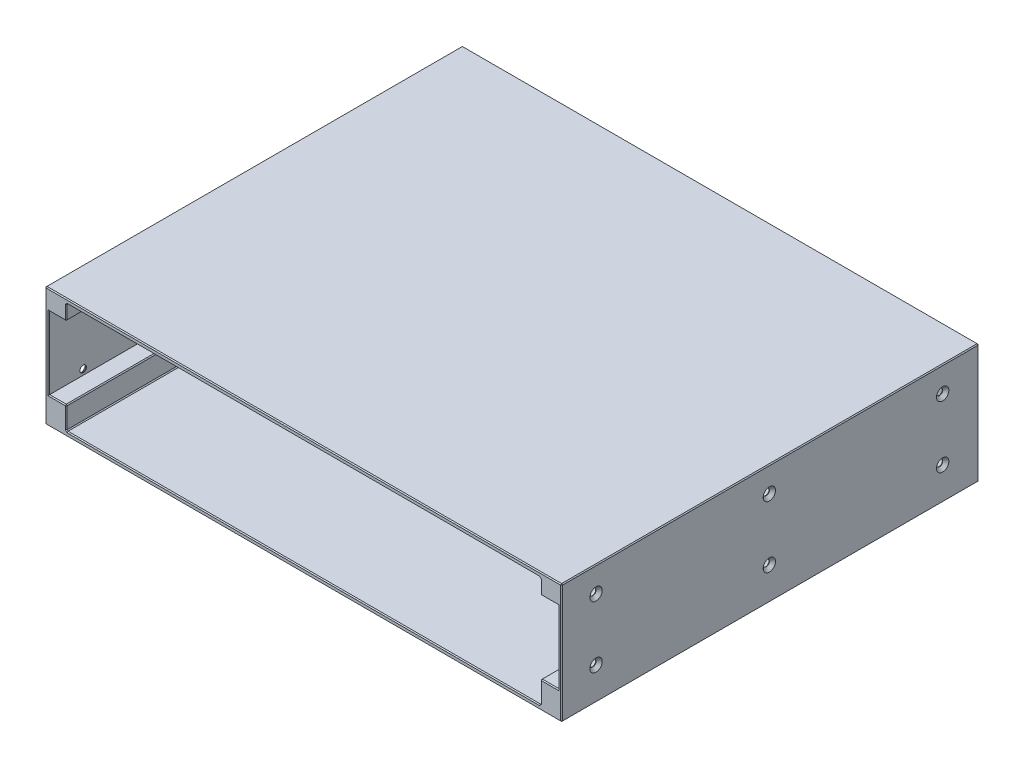
SolidWorks part; units mm, degrees
ref_plane "Front" through (0, 0, 0) normal (0, 0, 1) x (1, 0, 0)
ref_plane "Top" through (0, 0, 0) normal (0, 1, 0) x (1, 0, 0)
ref_plane "Right" through (0, 0, 0) normal (1, 0, 0) x (0, 0, -1)
sketch "Sketch1" plane through (0, 0, 0) normal (0, 0, 1) x (1, 0, 0)
  line L1 (-138, -30) -> (138, -30)
  line L2 (-138, -30) -> (-138, 30)
  line L3 (-138, 30) -> (138, 30)
  line L4 (138, -30) -> (138, 30)
  line L5 (-138, -30) -> (138, 30) construction
  line L6 (-138, 30) -> (138, -30) construction
  point P0 (0, 0)
  dimension "D1" = 276
  dimension "D2" = 60
extrude "Walls" add sketch "Sketch1" along normal blind 225 thin thin type one direction wall 2.5
sketch "Sketch2" plane through (0, 0, 0) normal (0, 0, 1) x (1, 0, 0)
  line L12 (140.5, -32.5) -> (140.5, 32.5)
  line L13 (140.5, 32.5) -> (-140.5, 32.5)
  line L14 (-140.5, 32.5) -> (-140.5, -32.5)
  line L15 (-140.5, -32.5) -> (140.5, -32.5)
  line L16 (140.5, -32.5) -> (140.5, 32.5)
  line L17 (140.5, 32.5) -> (-140.5, 32.5)
  line L18 (-140.5, 32.5) -> (-140.5, -32.5)
  line L19 (-140.5, -32.5) -> (140.5, -32.5)
  dimension "D1" = 0
extrude "Back Plate" add sketch "Sketch2" against normal blind 2
sketch "Sketch7" plane through (138.5, 0, 0) normal (1, 0, 0) x (0, 0, -1)
  line L0 (0, -30) -> (0, 30) construction
  line L1 (0, -17.75) -> (-225, -17.75)
  line L2 (0, -17.75) -> (0, 21.75)
  line L3 (0, 21.75) -> (-225, 21.75)
  line L4 (-225, -17.75) -> (-225, 21.75)
  line L5 (-225, -32.5) -> (-225, 32.5) construction
extrude "Drawer Slide Pocket" cut sketch "Sketch7" against normal up to next
sketch "Sketch8" plane through (138, 0, 0) normal (-1, 0, 0) x (0, 0, 1)
  line L0 (225, 32.5) -> (225, -32.5) construction
  line L1 (0, -30) -> (225, -30)
  line L2 (0, -30) -> (0, -17.75)
  line L3 (0, -17.75) -> (225, -17.75)
  line L4 (225, -30) -> (225, -17.75)
  line L6 (0, 30) -> (225, 30)
  line L7 (0, 30) -> (0, 21.75)
  line L8 (0, 21.75) -> (225, 21.75)
  line L9 (225, 30) -> (225, 21.75)
extrude "Drawer Slide Brackets" add sketch "Sketch8" along normal blind 9
sketch "Sketch9" plane through (140.5, 0, 0) normal (1, 0, 0) x (0, 0, -1)
  point P0 (-206.2857, -14.75)
  point P1 (-206.2857, 18.75)
  point P3 (-112, -14.75)
  point P5 (-112, 18.75)
  point P7 (-17.7143, -14.75)
  point P9 (-17.7143, 18.75)
hole_wizard "CSK for M3 SFHCS1" positions "Sketch9" profile "Sketch10" countersink size "M3" standard "ANSI Metric" end condition up to next
sketch "Sketch10" plane through (140.5, -14.75, 206.2857) normal (0, 1, 0) x (0, 0, -1)
  line L0 (0, 0) -> (0, 2)
  line L1 (0, 2) -> (1.8, 2)
  line L2 (1.7, 1.9) -> (1.7, 1.66)
  line L3 (1.7, 1.66) -> (3.36, 0)
  line L5 (3.36, 0) -> (0, 0)
  line L6 (-1.7, 1.66) -> (-3.36, 0) construction
  line L7 (1.8, 2) -> (1.7, 1.9)
  line L8 (-1.8, 2) -> (-1.7, 1.9) construction
  line L11 (0, -6.35) -> (0, 107.95) construction
  dimension "Thru Hole Dia." = 3.4
  dimension "Thru Hole Depth" = 2
  dimension "Near C'Sink Dia." = 6.72
  dimension "Near C'Sink Angle" = 90
  dimension "Far C'Sink Dia." = 3.6
  dimension "Far C'Sink Angle" = 90
mirror "Drawer Slide Pocket mirror" about plane through (0, 0, 0) normal (1, 0, 0) of "CSK for M3 SFHCS1", "Drawer Slide Pocket", "Drawer Slide Brackets"
sketch "Sketch3" plane through (0, -32.5, 0) normal (0, 1, 0) x (1, 0, 0)
  line L0 (0, 2) -> (0, -111.5) construction
  line L1 (-114.5192, -23.9808) -> (114.5192, -23.9808) construction
  line L2 (-114.5192, -23.9808) -> (-114.5192, -199.0192) construction
  line L3 (-114.5192, -199.0192) -> (114.5192, -199.0192) construction
  line L4 (114.5192, -23.9808) -> (114.5192, -199.0192) construction
  line L5 (-114.5192, -23.9808) -> (114.5192, -199.0192) construction
  line L6 (-114.5192, -199.0192) -> (114.5192, -23.9808) construction
  line L8 (0, -111.5) -> (0, -225) construction
  line L10 (-140.5, -23.9808) -> (-114.5192, -23.9808) construction
  line L11 (140.5, 2) -> (-140.5, 2) construction
  line L12 (-114.5192, -23.9808) -> (-114.5192, 2) construction
  line L13 (-57.2596, -23.9808) -> (-57.2596, -15.3205) construction
  line L14 (-114.5192, -32.641) -> (-107.0192, -28.3109)
  line L15 (-107.0192, -28.3109) -> (-107.0192, -19.6506)
  line L16 (-107.0192, -19.6506) -> (-114.5192, -15.3205)
  line L17 (-114.5192, -15.3205) -> (-122.0192, -19.6506)
  line L18 (-122.0192, -19.6506) -> (-122.0192, -28.3109)
  line L19 (-122.0192, -28.3109) -> (-114.5192, -32.641)
  line L20 (-57.2596, -15.3205) -> (-57.2596, -6.6603) construction
  line L21 (0, -111.5) -> (114.5192, -111.5) construction
  line L22 (122.0192, -28.3109) -> (114.5192, -32.641)
  line L23 (122.0192, -19.6506) -> (122.0192, -28.3109)
  line L24 (114.5192, -15.3205) -> (122.0192, -19.6506)
  line L25 (107.0192, -19.6506) -> (114.5192, -15.3205)
  line L26 (107.0192, -28.3109) -> (107.0192, -19.6506)
  line L27 (114.5192, -32.641) -> (107.0192, -28.3109)
  line L28 (122.0192, -203.3494) -> (122.0192, -194.6891)
  line L29 (114.5192, -207.6795) -> (122.0192, -203.3494)
  line L30 (107.0192, -203.3494) -> (114.5192, -207.6795)
  line L31 (107.0192, -194.6891) -> (107.0192, -203.3494)
  line L32 (114.5192, -190.359) -> (107.0192, -194.6891)
  line L33 (122.0192, -194.6891) -> (114.5192, -190.359)
  line L34 (-122.0192, -194.6891) -> (-114.5192, -190.359)
  line L35 (-122.0192, -203.3494) -> (-122.0192, -194.6891)
  line L36 (-114.5192, -207.6795) -> (-122.0192, -203.3494)
  line L37 (-107.0192, -203.3494) -> (-114.5192, -207.6795)
  line L38 (-107.0192, -194.6891) -> (-107.0192, -203.3494)
  line L39 (-114.5192, -190.359) -> (-107.0192, -194.6891)
  line L40 (-57.2596, -6.6603) -> (-57.2596, 2) construction
  line L41 (-114.5192, -10.9904) -> (-57.2596, -10.9904) construction
  line L42 (-57.2596, -10.9904) -> (0, -10.9904) construction
  line L43 (-140.5, -225) -> (-140.5, 2) construction
  line L44 (140.5, -225) -> (-140.5, -225) construction
  circle A0 centre (-114.5192, -23.9808) radius 7.5 construction
  point P0 (0, -111.5)
  dimension "D1" = 15
extrude "Foot Pocket" cut sketch "Sketch3" along normal blind 1.5 draft 45
sketch "Sketch4" plane through (0, 32.5, 0) normal (0, -1, 0) x (1, 0, 0)
  line L20 (-107.2192, 203.2339) -> (-114.5192, 207.4486)
  line L21 (-114.5192, 207.4486) -> (-121.8192, 203.2339)
  line L22 (-121.8192, 203.2339) -> (-121.8192, 194.8046)
  line L23 (-121.8192, 194.8046) -> (-114.5192, 190.5899)
  line L24 (-114.5192, 190.5899) -> (-107.2192, 194.8046)
  line L25 (-107.2192, 194.8046) -> (-107.2192, 203.2339)
  line L26 (-107.2192, 203.2339) -> (-114.5192, 207.4486)
  line L27 (-114.5192, 207.4486) -> (-121.8192, 203.2339)
  line L28 (-121.8192, 203.2339) -> (-121.8192, 194.8046)
  line L29 (-121.8192, 194.8046) -> (-114.5192, 190.5899)
  line L30 (-114.5192, 190.5899) -> (-107.2192, 194.8046)
  line L31 (-107.2192, 194.8046) -> (-107.2192, 203.2339)
  line L38 (-114.5192, 32.4101) -> (-121.8192, 28.1954)
  line L39 (-121.8192, 28.1954) -> (-121.8192, 19.7661)
  line L40 (-121.8192, 19.7661) -> (-114.5192, 15.5514)
  line L41 (-114.5192, 15.5514) -> (-107.2192, 19.7661)
  line L42 (-107.2192, 19.7661) -> (-107.2192, 28.1954)
  line L43 (-107.2192, 28.1954) -> (-114.5192, 32.4101)
  line L44 (-114.5192, 32.4101) -> (-121.8192, 28.1954)
  line L45 (-121.8192, 28.1954) -> (-121.8192, 19.7661)
  line L46 (-121.8192, 19.7661) -> (-114.5192, 15.5514)
  line L47 (-114.5192, 15.5514) -> (-107.2192, 19.7661)
  line L48 (-107.2192, 19.7661) -> (-107.2192, 28.1954)
  line L49 (-107.2192, 28.1954) -> (-114.5192, 32.4101)
  line L56 (114.5192, 207.4486) -> (107.2192, 203.2339)
  line L57 (107.2192, 203.2339) -> (107.2192, 194.8046)
  line L58 (107.2192, 194.8046) -> (114.5192, 190.5899)
  line L59 (114.5192, 190.5899) -> (121.8192, 194.8046)
  line L60 (121.8192, 194.8046) -> (121.8192, 203.2339)
  line L61 (121.8192, 203.2339) -> (114.5192, 207.4486)
  line L62 (114.5192, 207.4486) -> (107.2192, 203.2339)
  line L63 (107.2192, 203.2339) -> (107.2192, 194.8046)
  line L64 (107.2192, 194.8046) -> (114.5192, 190.5899)
  line L65 (114.5192, 190.5899) -> (121.8192, 194.8046)
  line L66 (121.8192, 194.8046) -> (121.8192, 203.2339)
  line L67 (121.8192, 203.2339) -> (114.5192, 207.4486)
  line L74 (121.8192, 19.7661) -> (121.8192, 28.1954)
  line L75 (114.5192, 15.5514) -> (121.8192, 19.7661)
  line L76 (107.2192, 19.7661) -> (114.5192, 15.5514)
  line L77 (107.2192, 28.1954) -> (107.2192, 19.7661)
  line L78 (114.5192, 32.4101) -> (107.2192, 28.1954)
  line L79 (121.8192, 28.1954) -> (114.5192, 32.4101)
  line L80 (121.8192, 19.7661) -> (121.8192, 28.1954)
  line L81 (114.5192, 15.5514) -> (121.8192, 19.7661)
  line L82 (107.2192, 19.7661) -> (114.5192, 15.5514)
  line L83 (107.2192, 28.1954) -> (107.2192, 19.7661)
  line L84 (114.5192, 32.4101) -> (107.2192, 28.1954)
  line L85 (121.8192, 28.1954) -> (114.5192, 32.4101)
  dimension "D1" = 0.2
  dimension "D2" = 0.2
  dimension "D3" = 0.2
  dimension "D4" = 0.2
extrude "Feet" [suppressed] add sketch "Sketch4" against normal blind 1.3 draft 45
chamfer "Deburs 1" distance 0.5 angle 45 34 edges at (-138.5, 2, 225) (-133.75, -17.75, 225) (-129, -17.75, 112.5) (-129, -23.875, 225) (0, -30, 225) (0, 30, 225) (-133.75, 21.75, 225) (-129, 21.75, 112.5) (-129, 25.875, 225) (-129, 30, 112.5) (0, 30, 0) (129, 30, 112.5) (129, 25.875, 225) (129, 21.75, 112.5) (133.75, 21.75, 225) (138.5, 2, 225) (133.75, -17.75, 225) (129, -17.75, 112.5) (129, -23.875, 225) (-129, -30, 112.5) (0, -30, 0) (129, -30, 112.5) (140.5, 0, 225) (0, -32.5, 225) (-140.5, 0, 225) (0, 32.5, 225) (-140.5, 0, -2) (-140.5, 32.5, 111.5) (0, 32.5, -2) (140.5, 32.5, 111.5) (140.5, 0, -2) (140.5, -32.5, 111.5) (0, -32.5, -2) (-140.5, -32.5, 111.5)
chamfer "Deburs 2" distance 0.5 angle 45 4 edges at (129, -23.875, 0) (129, 25.875, 0) (-129, 25.875, 0) (-129, -23.875, 0)
